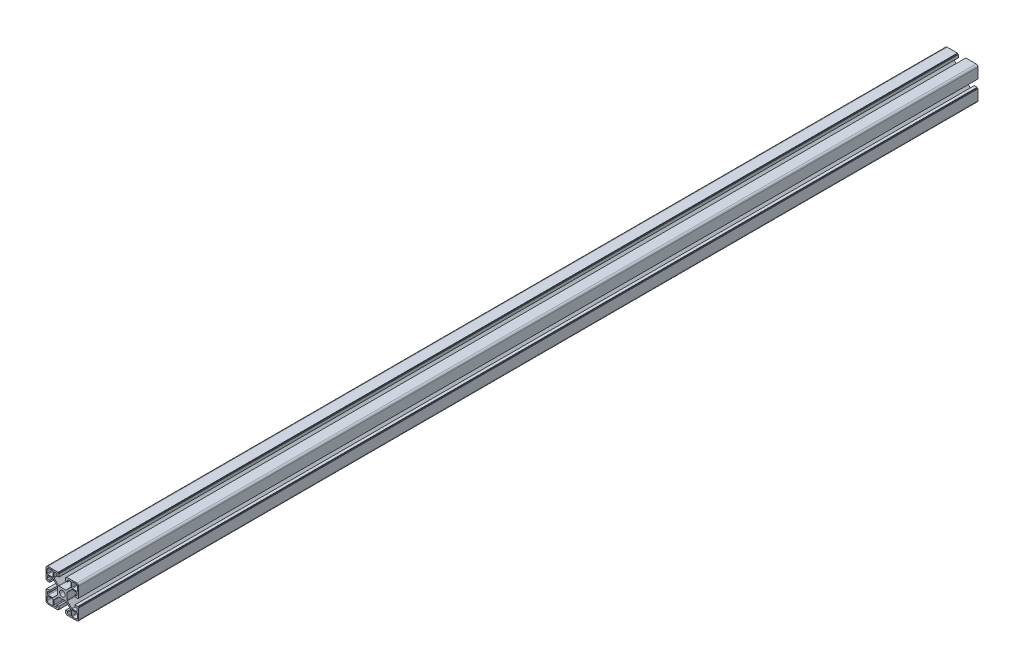
SolidWorks part; units mm, degrees
material "6063-T5"
ref_plane "Front Plane" through (0, 0, 0) normal (0, 0, 1) x (1, 0, 0)
ref_plane "Top Plane" through (0, 0, 0) normal (0, 1, 0) x (1, 0, 0)
ref_plane "Right Plane" through (0, 0, 0) normal (1, 0, 0) x (0, 0, -1)
sketch "Sketch1" plane through (0, 0, 0) normal (0, 0, 1) x (1, 0, 0)
  line L4 (20, 17.75) -> (20, 5.15)
  line L5 (0, -17.7813) -> (0, 18.2) construction
  line L6 (0, 0) -> (38.8613, 0) construction
  line L8 (18.6, 16.35) -> (18.6, 12.2)
  line L10 (11.4, 17.8) -> (11.4, 12.2)
  line L11 (-4.1, 5.85) -> (4.1, 5.85)
  line L14 (5.85, 4.1089) -> (5.85, -4.1089)
  line L17 (12.2, 11.4) -> (17.8, 11.4)
  line L24 (4.15, 19) -> (4.15, 15.4)
  line L25 (4.15, 15.4) -> (6.35, 15.4)
  line L26 (6.35, 15.4) -> (6.35, 16.95)
  line L27 (10.3, 17.2) -> (10.3, 12.0545)
  line L28 (10.0659, 11.489) -> (4.6659, 6.0845)
  line L29 (6.0841, 4.6743) -> (11.4708, 10.0655)
  line L30 (12.0367, 10.3) -> (17.2, 10.3)
  line L31 (18.2, 9.3) -> (18.2, 7.6)
  line L32 (16.95, 6.35) -> (15.4, 6.35)
  line L33 (15.4, 6.35) -> (15.4, 4.15)
  line L34 (15.4, 4.15) -> (19, 4.15)
  line L35 (18.6, 18.6) -> (18.6, -18.6) construction
  line L36 (-18.6, 18.6) -> (18.6, 18.6) construction
  line L37 (-20, 20) -> (20, 20) construction
  line L38 (20, 20) -> (20, -20) construction
  line L40 (7.6, 18.2) -> (9.3, 18.2)
  line L42 (4.15, 19) -> (5.15, 19)
  line L43 (5.15, 19) -> (5.15, 20)
  line L56 (-18.6, 18.6) -> (-18.6, -18.6) construction
  line L57 (-20, 20) -> (-20, -20) construction
  line L60 (5.15, 20) -> (17.75, 20)
  line L91 (-18.6, -18.6) -> (18.6, -18.6) construction
  line L92 (-20, -20) -> (20, -20) construction
  line L93 (12.2, 18.6) -> (16.35, 18.6)
  line L94 (17.9399, 17.9421) -> (20, 20) construction
  line L95 (0, 0) -> (11.4, 11.4094) construction
  line L101 (19, 4.15) -> (19, 5.15)
  line L102 (19, 5.15) -> (20, 5.15)
  line L104 (-5.85, 4.1089) -> (-5.85, -4.1089)
  line L105 (-19, 5.15) -> (-20, 5.15)
  line L106 (-19, 4.15) -> (-19, 5.15)
  line L107 (-12.2, 18.6) -> (-16.35, 18.6)
  line L108 (-5.15, 20) -> (-17.75, 20)
  line L109 (-5.15, 19) -> (-5.15, 20)
  line L110 (-4.15, 19) -> (-5.15, 19)
  line L111 (-7.6, 18.2) -> (-9.3, 18.2)
  line L112 (-15.4, 4.15) -> (-19, 4.15)
  line L113 (-15.4, 6.35) -> (-15.4, 4.15)
  line L114 (-16.95, 6.35) -> (-15.4, 6.35)
  line L115 (-18.2, 9.3) -> (-18.2, 7.6)
  line L116 (-12.0367, 10.3) -> (-17.2, 10.3)
  line L117 (-6.0841, 4.6743) -> (-11.4708, 10.0655)
  line L118 (-10.0659, 11.489) -> (-4.6659, 6.0845)
  line L119 (-10.3, 17.2) -> (-10.3, 12.0545)
  line L120 (-6.35, 15.4) -> (-6.35, 16.95)
  line L121 (-4.15, 15.4) -> (-6.35, 15.4)
  line L122 (-4.15, 19) -> (-4.15, 15.4)
  line L123 (-12.2, 11.4) -> (-17.8, 11.4)
  line L124 (-11.4, 17.8) -> (-11.4, 12.2)
  line L125 (-18.6, 16.35) -> (-18.6, 12.2)
  line L126 (-20, 17.75) -> (-20, 5.15)
  line L127 (-20, -17.75) -> (-20, -5.15)
  line L128 (-18.6, -16.35) -> (-18.6, -12.2)
  line L129 (-11.4, -17.8) -> (-11.4, -12.2)
  line L130 (-12.2, -11.4) -> (-17.8, -11.4)
  line L131 (-4.15, -19) -> (-4.15, -15.4)
  line L132 (-4.15, -15.4) -> (-6.35, -15.4)
  line L133 (-6.35, -15.4) -> (-6.35, -16.95)
  line L134 (-10.3, -17.2) -> (-10.3, -12.0545)
  line L135 (-10.0659, -11.489) -> (-4.6659, -6.0845)
  line L136 (-6.0841, -4.6743) -> (-11.4708, -10.0655)
  line L137 (-12.0367, -10.3) -> (-17.2, -10.3)
  line L138 (-18.2, -9.3) -> (-18.2, -7.6)
  line L139 (-16.95, -6.35) -> (-15.4, -6.35)
  line L140 (-15.4, -6.35) -> (-15.4, -4.15)
  line L141 (-15.4, -4.15) -> (-19, -4.15)
  line L142 (-7.6, -18.2) -> (-9.3, -18.2)
  line L143 (-4.15, -19) -> (-5.15, -19)
  line L144 (-5.15, -19) -> (-5.15, -20)
  line L145 (-5.15, -20) -> (-17.75, -20)
  line L146 (-12.2, -18.6) -> (-16.35, -18.6)
  line L147 (-19, -4.15) -> (-19, -5.15)
  line L148 (-19, -5.15) -> (-20, -5.15)
  line L149 (19, -5.15) -> (20, -5.15)
  line L150 (19, -4.15) -> (19, -5.15)
  line L151 (12.2, -18.6) -> (16.35, -18.6)
  line L152 (5.15, -20) -> (17.75, -20)
  line L153 (5.15, -19) -> (5.15, -20)
  line L154 (4.15, -19) -> (5.15, -19)
  line L155 (7.6, -18.2) -> (9.3, -18.2)
  line L156 (15.4, -4.15) -> (19, -4.15)
  line L157 (15.4, -6.35) -> (15.4, -4.15)
  line L158 (16.95, -6.35) -> (15.4, -6.35)
  line L159 (18.2, -9.3) -> (18.2, -7.6)
  line L160 (12.0367, -10.3) -> (17.2, -10.3)
  line L161 (6.0841, -4.6743) -> (11.4708, -10.0655)
  line L162 (10.0659, -11.489) -> (4.6659, -6.0845)
  line L163 (10.3, -17.2) -> (10.3, -12.0545)
  line L164 (6.35, -15.4) -> (6.35, -16.95)
  line L165 (4.15, -15.4) -> (6.35, -15.4)
  line L166 (4.15, -19) -> (4.15, -15.4)
  line L167 (12.2, -11.4) -> (17.8, -11.4)
  line L168 (-4.1, -5.85) -> (4.1, -5.85)
  line L169 (11.4, -17.8) -> (11.4, -12.2)
  line L170 (18.6, -16.35) -> (18.6, -12.2)
  line L171 (20, -17.75) -> (20, -5.15)
  circle A0 centre (0, 0) radius 3.4
  arc A7 (16.35, 18.6) -> (18.6, 16.35) centre (16.35, 16.35) cw
  arc A8 (20, 17.75) -> (17.75, 20) centre (17.75, 17.75) ccw
  arc A9 (6.35, 16.95) -> (7.6, 18.2) centre (7.6, 16.95) cw
  arc A10 (18.2, 7.6) -> (16.95, 6.35) centre (16.95, 7.6) cw
  arc A11 (17.2, 10.3) -> (18.2, 9.3) centre (17.2, 9.3) cw
  arc A12 (9.3, 18.2) -> (10.3, 17.2) centre (9.3, 17.2) cw
  arc A13 (4.6659, 6.0845) -> (4.1, 5.85) centre (4.1, 6.65) cw
  arc A14 (6.0841, 4.6743) -> (5.85, 4.1089) centre (6.65, 4.1089) ccw
  arc A15 (17.8, 11.4) -> (18.6, 12.2) centre (17.8, 12.2) ccw
  arc A16 (12.2, 18.6) -> (11.4, 17.8) centre (12.2, 17.8) ccw
  arc A17 (11.4, 12.2) -> (12.2, 11.4) centre (12.2, 12.2) ccw
  arc A18 (11.4708, 10.0655) -> (12.0367, 10.3) centre (12.0367, 9.5) cw
  arc A19 (10.3, 12.0545) -> (10.0659, 11.489) centre (9.5, 12.0545) cw
  arc A20 (-10.3, 12.0545) -> (-10.0659, 11.489) centre (-9.5, 12.0545) ccw
  arc A21 (-11.4708, 10.0655) -> (-12.0367, 10.3) centre (-12.0367, 9.5) ccw
  arc A22 (-11.4, 12.2) -> (-12.2, 11.4) centre (-12.2, 12.2) cw
  arc A23 (-12.2, 18.6) -> (-11.4, 17.8) centre (-12.2, 17.8) cw
  arc A24 (-17.8, 11.4) -> (-18.6, 12.2) centre (-17.8, 12.2) cw
  arc A25 (-6.0841, 4.6743) -> (-5.85, 4.1089) centre (-6.65, 4.1089) cw
  arc A26 (-4.6659, 6.0845) -> (-4.1, 5.85) centre (-4.1, 6.65) ccw
  arc A27 (-9.3, 18.2) -> (-10.3, 17.2) centre (-9.3, 17.2) ccw
  arc A28 (-17.2, 10.3) -> (-18.2, 9.3) centre (-17.2, 9.3) ccw
  arc A29 (-18.2, 7.6) -> (-16.95, 6.35) centre (-16.95, 7.6) ccw
  arc A30 (-6.35, 16.95) -> (-7.6, 18.2) centre (-7.6, 16.95) ccw
  arc A31 (-20, 17.75) -> (-17.75, 20) centre (-17.75, 17.75) cw
  arc A32 (-16.35, 18.6) -> (-18.6, 16.35) centre (-16.35, 16.35) ccw
  arc A33 (-16.35, -18.6) -> (-18.6, -16.35) centre (-16.35, -16.35) cw
  arc A34 (-20, -17.75) -> (-17.75, -20) centre (-17.75, -17.75) ccw
  arc A35 (-6.35, -16.95) -> (-7.6, -18.2) centre (-7.6, -16.95) cw
  arc A36 (-18.2, -7.6) -> (-16.95, -6.35) centre (-16.95, -7.6) cw
  arc A37 (-17.2, -10.3) -> (-18.2, -9.3) centre (-17.2, -9.3) cw
  arc A38 (-9.3, -18.2) -> (-10.3, -17.2) centre (-9.3, -17.2) cw
  arc A39 (-4.6659, -6.0845) -> (-4.1, -5.85) centre (-4.1, -6.65) cw
  arc A40 (-6.0841, -4.6743) -> (-5.85, -4.1089) centre (-6.65, -4.1089) ccw
  arc A41 (-17.8, -11.4) -> (-18.6, -12.2) centre (-17.8, -12.2) ccw
  arc A42 (-12.2, -18.6) -> (-11.4, -17.8) centre (-12.2, -17.8) ccw
  arc A43 (-11.4, -12.2) -> (-12.2, -11.4) centre (-12.2, -12.2) ccw
  arc A44 (-11.4708, -10.0655) -> (-12.0367, -10.3) centre (-12.0367, -9.5) cw
  arc A45 (-10.3, -12.0545) -> (-10.0659, -11.489) centre (-9.5, -12.0545) cw
  arc A46 (10.3, -12.0545) -> (10.0659, -11.489) centre (9.5, -12.0545) ccw
  arc A47 (11.4708, -10.0655) -> (12.0367, -10.3) centre (12.0367, -9.5) ccw
  arc A48 (11.4, -12.2) -> (12.2, -11.4) centre (12.2, -12.2) cw
  arc A49 (12.2, -18.6) -> (11.4, -17.8) centre (12.2, -17.8) cw
  arc A50 (17.8, -11.4) -> (18.6, -12.2) centre (17.8, -12.2) cw
  arc A51 (6.0841, -4.6743) -> (5.85, -4.1089) centre (6.65, -4.1089) cw
  arc A52 (4.6659, -6.0845) -> (4.1, -5.85) centre (4.1, -6.65) ccw
  arc A53 (9.3, -18.2) -> (10.3, -17.2) centre (9.3, -17.2) ccw
  arc A54 (17.2, -10.3) -> (18.2, -9.3) centre (17.2, -9.3) ccw
  arc A55 (18.2, -7.6) -> (16.95, -6.35) centre (16.95, -7.6) ccw
  arc A56 (6.35, -16.95) -> (7.6, -18.2) centre (7.6, -16.95) ccw
  arc A57 (20, -17.75) -> (17.75, -20) centre (17.75, -17.75) cw
  arc A58 (16.35, -18.6) -> (18.6, -16.35) centre (16.35, -16.35) ccw
  point P0 (0, 0)
  point P16 (-5.85, 0)
  point P66 (0, 5.85)
  point P120 (5.85, 0)
  point P218 (0, -5.85)
  dimension "D5" = 6.8
  dimension "D6" = 1.4
  dimension "D15" = 5.85
  dimension "D44" = 2.25
  dimension "D25" = 1.25
  dimension "D26" = 1
  dimension "D27" = 0.8
  dimension "D7" = 1.1
  dimension "D8" = 1.1
  dimension "D9" = 1.8
  dimension "D10" = 2.2
  dimension "D11" = 4.6
  dimension "D12" = 1.8
  dimension "D13" = 2.2
  dimension "D14" = 5.85
  dimension "D16" = 1.4
  dimension "D17" = 4.15
  dimension "D18" = 1
  dimension "D19" = 1
  dimension "D20" = 10.3
  dimension "D21" = 4.15
  dimension "D22" = 2
  dimension "D23" = 45.024
  dimension "D24" = 1
  dimension "D41" = 10.3
  dimension "D60" = 14.15
  dimension "D73" = 1
  dimension "D74" = 1
  dimension "D82" = 14.15
  dimension "D3" = 4.6
extrude "Boss-Extrude1" add sketch "Sketch1" along normal blind 1100
sketch "Sketch2" plane through (0, 20, 0) normal (0, 1, 0) x (1, 0, 0)
  line L0 (-20, -1100) -> (-20, 0) construction
  line L1 (-20, -600) -> (20, -600)
  line L2 (-20, -600) -> (-20, -1100)
  line L3 (-20, -1100) -> (20, -1100)
  line L4 (20, -600) -> (20, -1100)
  line L5 (-5.15, 0) -> (-17.75, 0) construction
  dimension "D1" = 600
